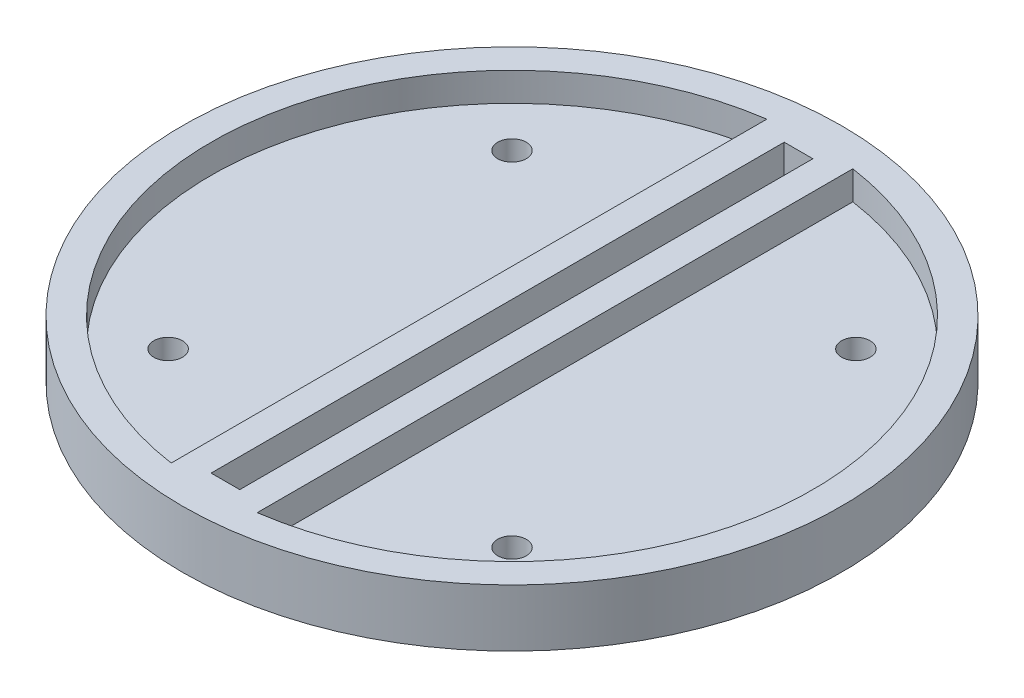
SolidWorks part; units mm, degrees
material "ABS"
ref_plane "Front Plane" through (0, 0, 0) normal (0, 0, 1) x (1, 0, 0)
ref_plane "Top Plane" through (0, 0, 0) normal (0, 1, 0) x (1, 0, 0)
ref_plane "Right Plane" through (0, 0, 0) normal (1, 0, 0) x (0, 0, -1)
sketch "Sketch5" plane through (0, 0, 0) normal (0, 1, 0) x (1, 0, 0)
  circle A0 centre (0, 0) radius 73.025
  circle A1 centre (38.1, 38.1) radius 3.175
  circle A2 centre (38.1, -38.1) radius 3.175
  circle A3 centre (-38.1, 38.1) radius 3.175
  circle A4 centre (-38.1, -38.1) radius 3.175
extrude "PlateBase" add sketch "Sketch5" along normal blind 6.35
sketch "Sketch6" plane through (0, 6.35, 0) normal (0, 1, 0) x (1, 0, 0)
  line L1 (3.175, 0) -> (3.175, 72.9559)
  line L3 (3.175, 0) -> (3.175, -72.9559)
  line L4 (0, 0) -> (3.175, 0)
  line L5 (-3.175, 0) -> (-3.175, 72.9559)
  line L6 (-9.525, 0) -> (-9.525, 72.4011)
  line L7 (-9.525, 0) -> (-9.525, -72.4011)
  line L8 (-3.175, 0) -> (-3.175, -72.9559)
  line L9 (9.525, 0) -> (9.525, 72.4011)
  line L10 (9.525, 0) -> (9.525, -72.4011)
  circle A0 centre (0, 0) radius 73.025 construction
  circle M4 centre (0, 0) radius 73.025
extrude "PlateTop" add sketch "Sketch6" along normal blind 6.35 contours L8 L5 L6 L7 M4 | L10 L9 L1 L3 M4 region at (6.346, 6.35, 0) region at (-6.346, 6.35, 0)
sketch "Sketch9" plane through (0, 6.35, 0) normal (0, 1, 0) x (1, 0, 0)
  circle A0 centre (0, 0) radius 66.675
  circle A1 centre (0, 0) radius 73.025
extrude "PlateWalls" add sketch "Sketch9" along normal blind 6.35
sketch "Sketch11" plane through (0, 6.35, 0) normal (0, 1, 0) x (1, 0, 0)
  line L1 (-3.175, 66.5994) -> (-3.175, -66.5994) construction
  line L3 (-3.175, -63.5) -> (3.175, -63.5)
  line L4 (-3.175, 66.5994) -> (-3.175, -66.5994) construction
  line L5 (3.175, -63.5) -> (3.175, -66.5994)
  line L6 (-3.175, 63.5) -> (3.175, 63.5)
  line L7 (3.175, -66.5994) -> (3.175, 66.5994) construction
  line L8 (3.175, 63.5) -> (3.175, 66.5994)
  line L9 (-3.175, 66.5994) -> (-3.175, 63.5)
  line L10 (-3.175, -63.5) -> (-3.175, -66.5994)
  arc A0 (3.175, 66.5994) -> (-3.175, 66.5994) centre (0, 0) ccw
  arc A1 (3.175, -66.5994) -> (-3.175, -66.5994) centre (0, 0) cw
extrude "PlateSlotEnds" add sketch "Sketch11" along normal blind 6.35 from surface starting at face at (0, 6.35, 0)
